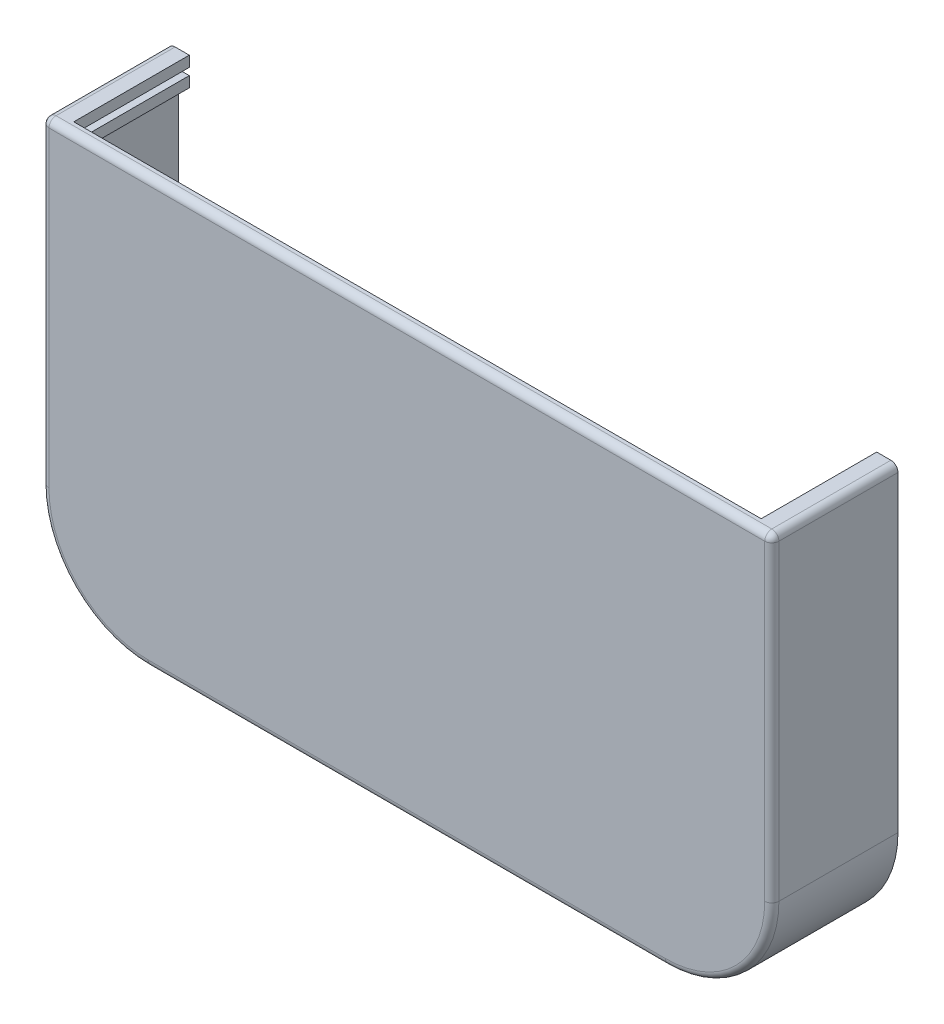
SolidWorks part; units mm, degrees
ref_plane "Plan de face" through (0, 0, 0) normal (0, 0, 1) x (1, 0, 0)
ref_plane "Plan de dessus" through (0, 0, 0) normal (0, 1, 0) x (1, 0, 0)
ref_plane "Plan de droite" through (0, 0, 0) normal (1, 0, 0) x (0, 0, -1)
sketch "Esquisse1" plane through (0, 0, 0) normal (0, 0, 1) x (1, 0, 0)
  line L1 (-36.5, -30) -> (36.5, -30)
  line L2 (-51.5, -15) -> (-51.5, 30)
  line L3 (-51.5, 30) -> (51.5, 30)
  line L4 (51.5, -15) -> (51.5, 30)
  line L5 (-51.5, -30) -> (51.5, 30) construction
  line L6 (-51.5, 30) -> (51.5, -30) construction
  arc A0 (36.5, -30) -> (51.5, -15) centre (36.5, -15) ccw
  arc A1 (-36.5, -30) -> (-51.5, -15) centre (-36.5, -15) cw
  point P0 (0, 0)
  dimension "D3" = 15
  dimension "D1" = 60
  dimension "D2" = 103
extrude "Boss.-Extru.1" add sketch "Esquisse1" along normal blind 17.8
sketch "Esquisse2" plane through (0, 0, 0) normal (0, 0, -1) x (-1, 0, 0)
  line L0 (-51.5, 30) -> (51.5, 30) construction
  line L1 (-50, 28.5) -> (-48.5, 28.5)
  line L2 (-50, 28.5) -> (-50, 27.5)
  line L3 (-50, 27.5) -> (50, 27.5)
  line L4 (50, 28.5) -> (50, 27.5)
  line L5 (48.5, 28.5) -> (50, 28.5)
  line L7 (-48.5, 28.5) -> (-48.5, 30)
  line L8 (-48.5, 30) -> (48.5, 30)
  line L9 (48.5, 28.5) -> (48.5, 30)
  point P4 (0, 28.5)
  point P12 (0, 30)
  dimension "D1" = 100
  dimension "D2" = 1
  dimension "D3" = 1.5
  dimension "D4" = 1.5
extrude "Enlèv. mat.-Extru.1" cut sketch "Esquisse2" against normal offset from surface (16.3 mm away) 1.5 up to face at (0, -6.0355, 17.8)
shell "Coque2" thickness 1.5 removed face at (0, 13.7705, 0)
sketch "Esquisse3" plane through (0, 0, 0) normal (0, 0, -1) x (-1, 0, 0)
  line L0 (-48.5, 28.5) -> (-48.5, 23.9827) construction
  line L1 (48.5, 28.5) -> (48.5, 24.1859) construction
  line L2 (50, 26) -> (-50, 26) construction
  line L3 (-48.5, 27.5) -> (48.5, 27.5)
  line L4 (-48.5, 27.5) -> (-48.5, 26)
  line L5 (-48.5, 26) -> (48.5, 26)
  line L6 (48.5, 27.5) -> (48.5, 26)
  line L7 (50, 27.5) -> (-50, 27.5) construction
extrude "Enlèv. mat.-Extru.2" cut sketch "Esquisse3" against normal up to surface (16.3 mm away) up to face at (0, 28.625, 16.3)
sketch "Esquisse4" plane through (0, 0, 16.3) normal (0, 0, -1) x (-1, 0, 0)
  line L0 (0, 30) -> (0, -30) construction
  line L1 (-48.5, 30) -> (48.5, 30) construction
  line L2 (36.5, -30) -> (-36.5, -30) construction
  circle A0 centre (0, 0) radius 2.75
  dimension "D1" = 5.5
extrude "Boss.-Extru.2" add sketch "Esquisse4" along normal up to surface (16.3 mm away) up to face at (0, 10.7998, 0)
fillet "Congé3" radius 2.5 1 edges at (-2.75, 0, 16.3)
sketch "Esquisse5" plane through (0, 0, 0) normal (0, 0, -1) x (-1, 0, 0)
  circle A0 centre (0, 0) radius 1
  dimension "D1" = 2
extrude "Enlèv. mat.-Extru.3" cut sketch "Esquisse5" against normal blind 5
sketch "Esquisse6" [suppressed] plane through (0, 0, 16.3) normal (0, 0, -1) x (-1, 0, 0)
  line L0 (-50, -15) -> (-36.5, -28.5)
  line L1 (50, 25) -> (50, -15) construction
  line L2 (36.5, -28.5) -> (50, -15)
  arc A0 (-36.5, -28.5) -> (-50, -15) centre (-36.5, -15) cw
  arc A1 (50, -15) -> (36.5, -28.5) centre (36.5, -15) cw
  arc A2 (36.5, -28.5) -> (50, -15) centre (36.5, -15) ccw construction
sketch "Esquisse7" plane through (0, 0, 16.3) normal (0, 0, -1) x (-1, 0, 0)
  line L0 (-50, -15) -> (-36.5, -28.5)
  line L1 (36.5, -28.5) -> (50, -15)
  arc A0 (-36.5, -28.5) -> (-50, -15) centre (-36.5, -15) cw
  arc A1 (36.5, -28.5) -> (50, -15) centre (36.5, -15) ccw
extrude "Boss.-Extru.4" add sketch "Esquisse7" along normal up to surface (16.3 mm away) up to face at (0, 10.7998, 0)
fillet "Congé4" radius 1 15 edges at (50, 26, 8.15) (48.5, 26.75, 16.3) (49.25, 26, 16.3) (-48.5, 26.75, 16.3) (-50, 26, 8.15) (-49.25, 26, 16.3) (-36.5, -28.5, 8.15) (-50, -15, 8.15) (50, 5.5, 16.3) (50, -15, 8.15) (43.25, -21.75, 16.3) (36.5, -28.5, 8.15) (0, -28.5, 16.3) (-43.25, -21.75, 16.3) (-50, 5.5, 16.3)
sketch "Esquisse8" plane through (0, 0, 0) normal (0, 0, -1) x (-1, 0, 0)
  line L0 (36.5, -30) -> (-36.5, -30) construction
  line L1 (-51.5, -15) -> (-51.5, 30) construction
  line L2 (0, 0) -> (0, -22.552) construction
  circle A0 centre (-45, -23.5) radius 1
  circle A1 centre (45, -23.5) radius 1
  dimension "D3" = 2
  dimension "D1" = 6.5
  dimension "D2" = 6.5
extrude "Boss.-Extru.5" add sketch "Esquisse8" along normal blind 3
fillet "Congé5" radius 0.5 4 edges at (-44, -23.5, 0) (44, -23.5, 0) (-44, -23.5, -3) (44, -23.5, -3)
fillet "Congé6" radius 1 8 edges at (-51.5, 7.5, 17.8) (-47.1066, -25.6066, 17.8) (0, -30, 17.8) (47.1066, -25.6066, 17.8) (0, 30, 17.8) (-51.5, 30, 8.9) (51.5, 7.5, 17.8) (51.5, 30, 8.9)
